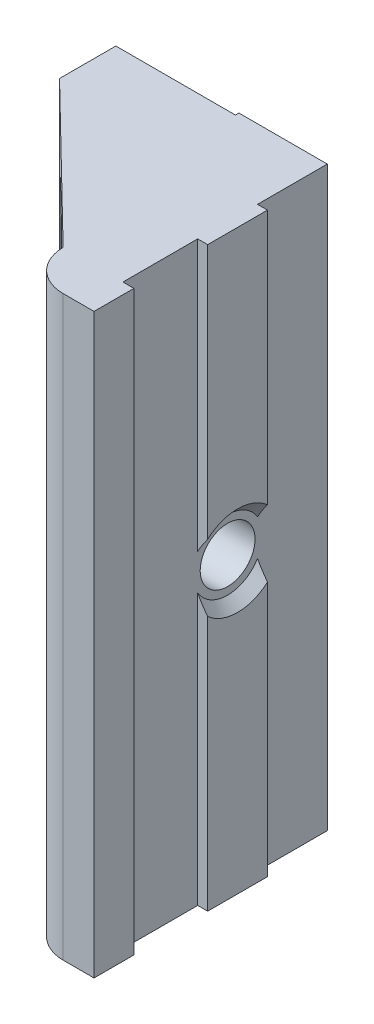
SolidWorks part; units mm, degrees
ref_plane "Top Plane" through (0, 0, 0) normal (0, 0, 1) x (1, 0, 0)
ref_plane "Right Plane" through (0, 0, 0) normal (0, 1, 0) x (1, 0, 0)
ref_plane "Front Plane" through (0, 0, 0) normal (1, 0, 0) x (0, 0, -1)
sketch "Sketch1" plane through (0, 0, 0) normal (0, 0, 1) x (1, 0, 0)
  line L0 (30.861, -28.956) -> (30.861, 28.956) construction
  line L1 (30.861, 28.956) -> (10, 28.956) construction
  line L2 (30.861, 28.956) -> (30.861, -28.956) construction
  line L3 (30.861, -28.956) -> (10, -28.956) construction
  line L4 (-30.861, 28.956) -> (-30.861, -28.956)
  line L5 (30.861, 28.956) -> (19.431, 28.956) construction
  line L6 (-30.861, -28.956) -> (-30.861, 28.956) construction
  line L7 (-30.861, 0) -> (-24.8158, 0) construction
  line L8 (-24.8158, -19.05) -> (24.8412, -19.05) construction
  line L9 (-24.8158, -19.05) -> (-24.8158, 19.05) construction
  line L10 (-24.8158, 19.05) -> (24.8412, 19.05) construction
  line L11 (24.8412, -19.05) -> (24.8412, 19.05) construction
  line L12 (-10, 28.956) -> (-30.861, 28.956)
  line L14 (-10, -28.956) -> (-10, 28.956)
  line L16 (10, -28.956) -> (10, 28.956) construction
  line L17 (-10, -28.956) -> (-30.861, -28.956)
  circle A0 centre (24.8412, 19.05) radius 3.25 construction
  circle A1 centre (24.8412, -19.05) radius 3.25 construction
  circle A2 centre (-24.8158, -19.05) radius 3.25
  circle A3 centre (-24.8158, 19.05) radius 3.25
  arc A4 (-24.8158, 16.3957) -> (-24.8158, 21.7043) centre (-24.8158, 19.05) ccw construction
  arc A5 (24.8412, -21.7043) -> (24.8412, -16.3957) centre (24.8412, -19.05) ccw construction
  dimension "D1" = 6.5
  dimension "D3" = 20
extrude "Boss-Extrude1" add sketch "Sketch1" along normal blind 6 contours A3 | L17 L14 L12 L4 A3 A2 | A2 | A3 | A2 | L14 L12 L4 L17 region at (-20.1756, 0, 0) region at (-24.8158, -19.05, 0) region at (-24.8158, 19.05, 0)
sketch "Sketch7" plane through (0, -28.956, 0) normal (0, -1, 0) x (1, 0, 0)
  line L0 (-30.861, 6) -> (-16, 20.5)
  line L2 (-10, 20.5) -> (-10, 6)
  line L3 (-10, 6) -> (-30.861, 6)
  line L6 (-16, 20.5) -> (-10, 20.5) construction
  line L7 (-10, 20.5) -> (-8.9, 20.5)
  line L8 (-16, 20.5) -> (-16, 24.5)
  line L9 (-16, 24.5) -> (-8.9, 24.5)
  line L10 (-8.9, 20.5) -> (-8.9, 24.5)
  line L11 (-30.861, 6) -> (-30.861, 0) construction
  line L12 (-10, 0) -> (-30.861, 0) construction
  point P13 (0, 0)
  dimension "D1" = 20.5
  dimension "D2" = 4
  dimension "D3" = 8.9
extrude "Boss-Extrude2" add sketch "Sketch7" against normal up to surface (57.912 mm away) up to face at (-20.4305, 28.956, 3)
sketch "Sketch8" plane through (0, 0, 0) normal (0, 0, -1) x (-1, 0, 0)
  circle A0 centre (24.8158, -19.05) radius 3.25
  circle A1 centre (24.8158, 19.05) radius 3.25
  circle A2 centre (24.8158, -19.05) radius 3.25 construction
extrude "Cut-Extrude4" cut sketch "Sketch8" against normal through all
sketch "Sketch9" plane through (0, 0, 0) normal (0, 0, -1) x (-1, 0, 0)
  circle A0 centre (24.8158, -19.05) radius 5.25
  circle A1 centre (24.8158, 19.05) radius 5.25
  dimension "D1" = 10.5
extrude "Cut-Extrude5" cut sketch "Sketch9" against normal through all from vertex starting at point (-30.861, -28.956, 6)
sketch "Sketch10" plane through (-10, 0, 0) normal (1, 0, 0) x (0, 0, -1)
  line L0 (-10, 0) -> (0, 0) construction
  line L1 (0, -28.956) -> (0, 28.956) construction
  line L4 (-10, -2.75) -> (-10, 2.75) construction
  circle A0 centre (-10, 0) radius 2.75
  dimension "D2" = 5.5
  dimension "D1" = 10
extrude "Cut-Extrude6" cut sketch "Sketch10" against normal through all
sketch "Sketch11" plane through (-10, 0, 0) normal (1, 0, 0) x (0, 0, -1)
  line L1 (-10, -5.25) -> (-10, 5.25) construction
  circle A0 centre (-10, 0) radius 5.25
  dimension "D1" = 10.5
extrude "Cut-Extrude7" cut sketch "Sketch11" against normal through all from offset 9 offset against normal yes
sketch "Sketch12" plane through (0, 28.956, 0) normal (0, 1, 0) x (1, 0, 0)
  line L1 (-30.861, 0) -> (-18.861, 0)
  line L2 (-30.861, 0) -> (-30.861, -0.35)
  line L3 (-30.861, -0.35) -> (-18.861, -0.35)
  line L4 (-18.861, 0) -> (-18.861, -0.35)
  dimension "D1" = 0.35
  dimension "D2" = 12
extrude "Cut-Extrude8" cut sketch "Sketch12" against normal through all
fillet "Fillet1" radius 4 1 edges at (-16, 0, 24.5)
sketch "Sketch13" plane through (-10, 0, 0) normal (1, 0, 0) x (0, 0, -1)
  line L0 (-10, 28.956) -> (-10, -28.956) construction
  line L1 (-20.5, 28.956) -> (0, 28.956) construction
  line L2 (-20.5, -28.956) -> (0, -28.956) construction
  line L4 (-7, -28.956) -> (-13, -28.956)
  line L5 (-7, -28.956) -> (-7, 28.956)
  line L6 (-7, 28.956) -> (-13, 28.956)
  line L7 (-13, -28.956) -> (-13, 28.956)
  circle A0 centre (-10, 0) radius 2.75
  circle A1 centre (-10, 0) radius 2.75 construction
  point P6 (-10, 0)
  dimension "D1" = 6
extrude "Boss-Extrude3" add sketch "Sketch13" along normal blind 1
chamfer "Chamfer1" distance 2.5 angle 45 1 edges at (-19, 0, 4.75)
sketch "Sketch14" plane through (-9, 0, 0) normal (1, 0, 0) x (0, 0, -1)
  circle A0 centre (-10, 0) radius 3.5
  dimension "D1" = 7
extrude "Cut-Extrude9" cut sketch "Sketch14" against normal up to surface (1 mm away) up to face at (-10, 0, 16.75)
chamfer "Chamfer2" distance 1 angle 45 2 edges at (-9, 3.5, 10) (-9, -3.5, 10)
